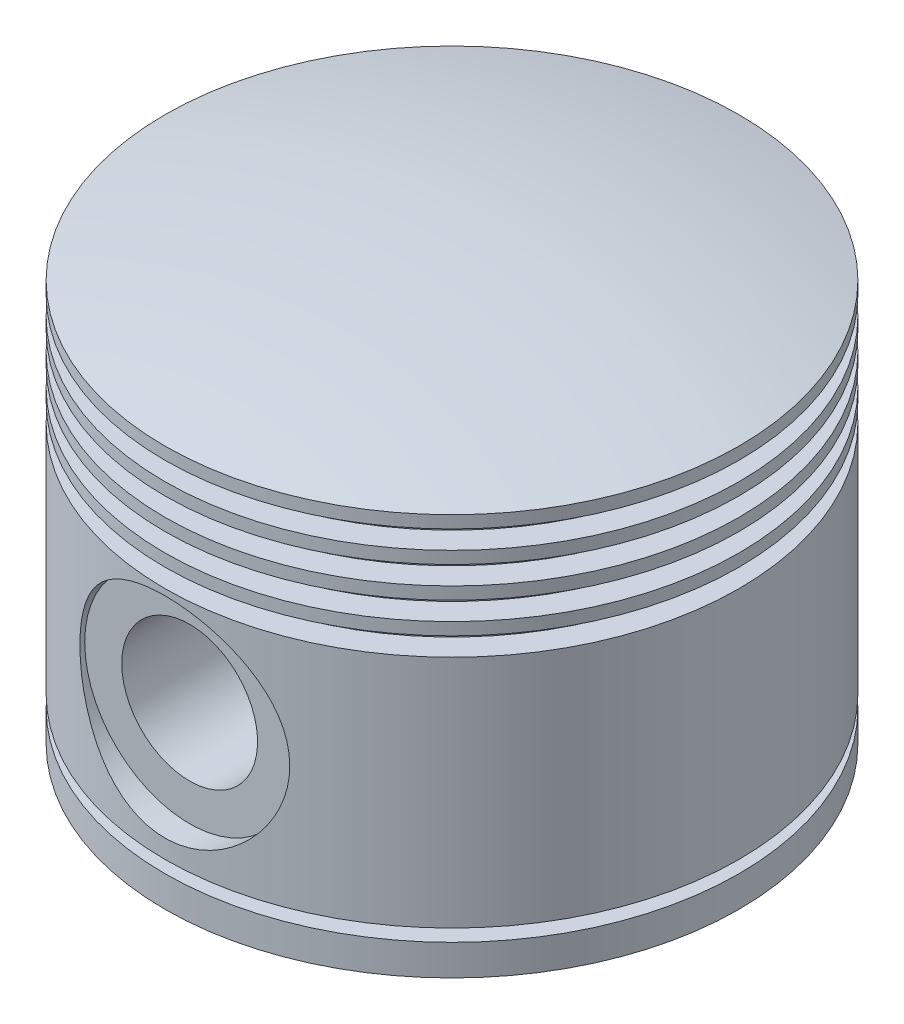
SolidWorks part; units mm, degrees
ref_plane "Front Plane" through (0, 0, 0) normal (0, 0, 1) x (1, 0, 0)
ref_plane "Top Plane" through (0, 0, 0) normal (0, 1, 0) x (1, 0, 0)
ref_plane "Right Plane" through (0, 0, 0) normal (1, 0, 0) x (0, 0, -1)
sketch "Sketch1" plane through (0, 0, 0) normal (0, 0, 1) x (1, 0, 0)
  line L0 (37, 0) -> (46.5, 0)
  line L1 (46.5, 0) -> (46.5, 5)
  line L2 (37, 65) -> (0, 65)
  line L3 (0, 65) -> (0, 0) construction
  line L5 (37, 0) -> (37, 65)
  line L6 (46.5, 63) -> (42.5, 63)
  line L8 (46.5, 60) -> (42.5, 60)
  line L9 (42.5, 63) -> (42.5, 60)
  line L11 (46.5, 58) -> (42.5, 58)
  line L12 (42.5, 58) -> (42.5, 55)
  line L13 (46.5, 55) -> (42.5, 55)
  line L15 (46.5, 53) -> (42.5, 53)
  line L16 (42.5, 53) -> (42.5, 50)
  line L17 (46.5, 50) -> (42.5, 50)
  line L19 (46.5, 48) -> (42.5, 48)
  line L20 (42.5, 48) -> (42.5, 45)
  line L21 (46.5, 45) -> (42.5, 45)
  line L22 (46.5, 63) -> (46.5, 65)
  line L23 (46.5, 58) -> (46.5, 60)
  line L24 (46.5, 53) -> (46.5, 55)
  line L25 (46.5, 48) -> (46.5, 50)
  line L26 (46.5, 7) -> (46.5, 45)
  line L27 (46.5, 7) -> (42.5, 7)
  line L29 (46.5, 5) -> (42.5, 5)
  line L30 (42.5, 7) -> (42.5, 5)
  line L31 (0, 65) -> (0, 70.8095)
  arc A0 (0, 70.8095) -> (46.5, 65) centre (0, -118.1905) cw
  dimension "D3" = 189
  dimension "D1" = 65
  dimension "D2" = 93
  dimension "D4" = 2
  dimension "D5" = 4
  dimension "D6" = 3
  dimension "D7" = 9.5
  dimension "D9" = 5
  dimension "D10" = 4
  dimension "D11" = 2
  dimension "D8" = 4
revolve "Revolve1" add sketch "Sketch1" angle 360 about L31
sketch "Sketch2" plane through (0, 0, 0) normal (0, 0, 1) x (1, 0, 0)
  circle A2 centre (0, 27) radius 18
  circle A3 centre (0, 27) radius 11
  circle A4 centre (0, 27) radius 17
  dimension "D1" = 36
  dimension "D2" = 22
  dimension "D3" = 34
  dimension "D4" = 27
extrude "Boss-Extrude2" add sketch "Sketch2" against normal up to next from offset 25 contours A2 offset against normal yes
extrude "Cut-Extrude1" cut sketch "Sketch2<3>" against normal up to surface (0.7811 mm away) from offset 42.5 contours A4 up to face at (0, 45, -46.5) offset against normal yes
sketch "Sketch2<3>" plane through (0, 0, 0) normal (0, 0, 1) x (1, 0, 0) same geometry as "Sketch2"
extrude "Cut-Extrude2" cut sketch "Sketch2<4>" against normal blind 90 contours A3 region at (0, 27, 0)
sketch "Sketch2<4>" plane through (0, 0, 0) normal (0, 0, 1) x (1, 0, 0) same geometry as "Sketch2"
mirror "Mirror1" about plane through (0, 0, 0) normal (0, 0, 1) of "Cut-Extrude2", "Cut-Extrude1", "Boss-Extrude2"
